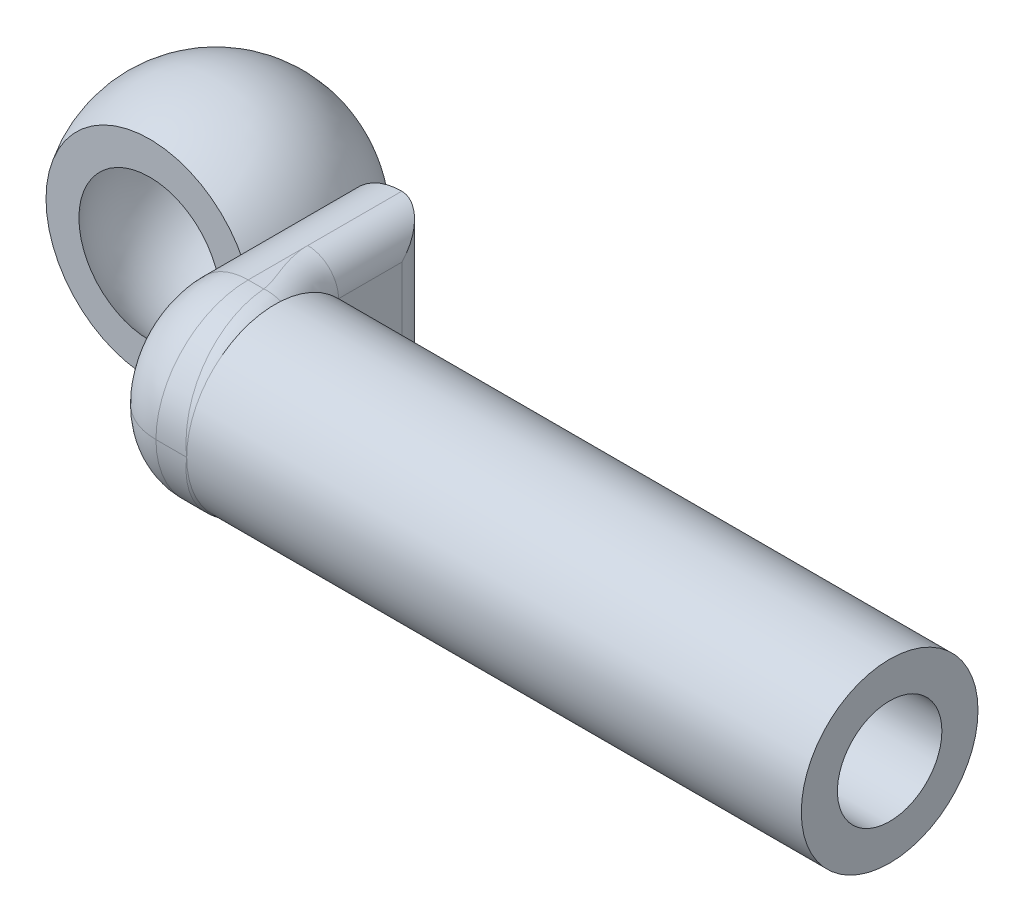
SolidWorks part; units mm, degrees
ref_plane "Front Plane" through (0, 0, 0) normal (0, 0, 1) x (1, 0, 0)
ref_plane "Top Plane" through (0, 0, 0) normal (0, 1, 0) x (1, 0, 0)
ref_plane "Right Plane" through (0, 0, 0) normal (1, 0, 0) x (0, 0, -1)
sketch "Sketch1" plane through (0, 0, 0) normal (0, 1, 0) x (1, 0, 0)
  line L0 (0, 0) -> (0, 6.3)
  line L1 (0, 7.15) -> (0, -0.85)
  line L2 (0, 0) -> (0, 1)
  arc A1 (0, 6.3) -> (0, 0) centre (0, 3.15) ccw
  arc A2 (0, 7.15) -> (0, -0.85) centre (0, 3.15) ccw
revolve "Revolve1" add sketch "Sketch1" angle 360 about L0 region at (-0.0894, 0, 0.425)
sketch "Sketch3" plane through (0, 0, 0) normal (0, 1, 0) x (1, 0, 0)
  line L2 (0, 0.15) -> (-4, 0.15)
  line L4 (0, -0.85) -> (-4, -0.85)
  line L5 (-4, 0.15) -> (-4, -0.85)
  line L6 (0, 0.15) -> (4, 0.15)
  line L8 (0, -0.85) -> (4, -0.85)
  line L9 (4, 0.15) -> (4, -0.85)
  circle A0 centre (0, 3.15) radius 4 construction
extrude "Cut-Extrude4" cut sketch "Sketch3" against normal blind 10 and the other way blind 10
sketch "Sketch4" plane through (0, 0, 0) normal (0, 1, 0) x (1, 0, 0)
  line L2 (-4, 1) -> (0, 1)
  line L3 (-4, 1) -> (-4, 0)
  line L4 (-4, 0) -> (0, 0)
  line L6 (0, 1) -> (4, 1)
  line L8 (0, 0) -> (4, 0)
  line L9 (4, 1) -> (4, 0)
extrude "Cut-Extrude5" cut sketch "Sketch4" against normal blind 10 and the other way blind 10
sketch "Sketch5" plane through (0, 0, 0) normal (1, 0, 0) x (0, 0, -1)
  line L2 (-3.9953, 0) -> (-3.9953, -3)
  line L4 (-3.9953, 0) -> (-3.9953, 3)
  line L5 (-3.9953, 3) -> (4.0047, 3)
  line L6 (4.0047, 0) -> (4.0047, 3)
  line L7 (-3.9953, -3) -> (4.0047, -3)
  line L8 (4.0047, -3) -> (4.0047, 0)
  dimension "D1" = 8
  dimension "D2" = 3
extrude "Boss-Extrude2" add sketch "Sketch5" along normal blind 3 from offset 3.2
sketch "Sketch6" plane through (6.2, 0, 0) normal (1, 0, 0) x (0, 0, -1)
  line L0 (4.0047, -3) -> (4.0047, 3) construction
  line L1 (4.0047, 3) -> (-3.9953, 3) construction
  circle A0 centre (-1.1203, 0) radius 1.7
  circle A1 centre (-1.1203, 0) radius 2.875
  dimension "D1" = 5.125
  dimension "D2" = 3
extrude "Boss-Extrude3" add sketch "Sketch6" along normal blind 20
fillet "Fillet1" radius 3 2 edges at (4.7, -3, 3.9953) (4.7, 3, 3.9953)
fillet "Fillet2" radius 2 4 edges at (3.2, -3, -1.5047) (3.2, -2.1213, 3.1166) (3.2, 2.1213, 3.1166) (3.2, 3, -1.5047)
fillet "Fillet3" radius 1 5 edges at (6.2, -2.1213, 3.1166) (6.2, 2.1213, 3.1166) (6.2, -3, -1.5047) (6.2, 0, -4.0047) (6.2, 3, -1.5047)
